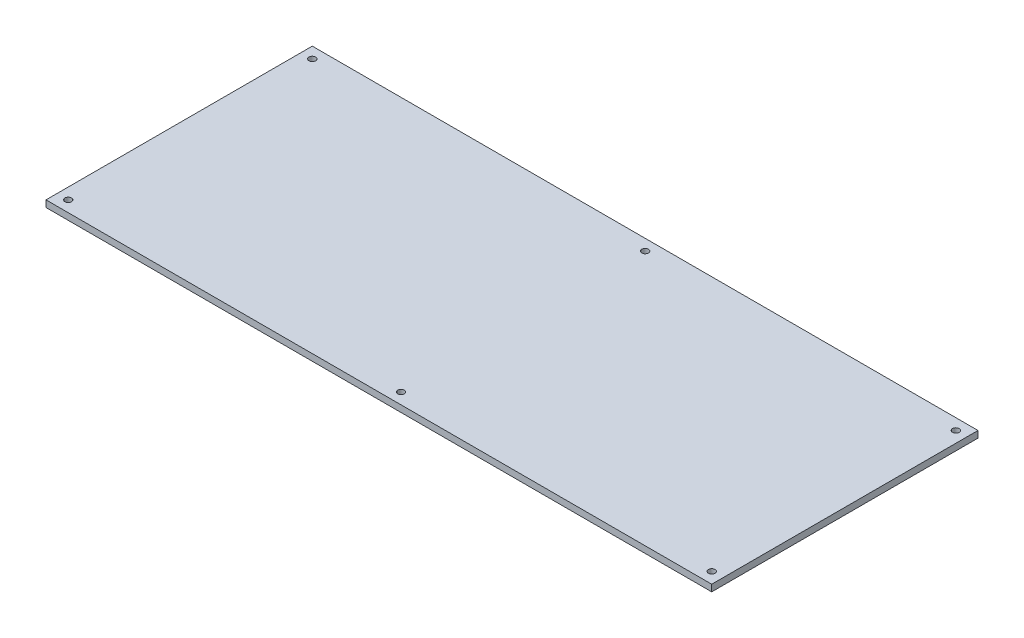
SolidWorks part; units mm, degrees
ref_plane "前视基准面" through (0, 0, 0) normal (0, 0, 1) x (1, 0, 0)
ref_plane "上视基准面" through (0, 0, 0) normal (0, 1, 0) x (1, 0, 0)
ref_plane "右视基准面" through (0, 0, 0) normal (1, 0, 0) x (0, 0, -1)
sketch "Sketch1" plane through (0, 0, 0) normal (0, 1, 0) x (1, 0, 0)
  line L0 (0, 0) -> (0, 75.008) construction
  line L1 (-150, 60) -> (150, 60)
  line L2 (-150, 60) -> (-150, -60)
  line L3 (-150, -60) -> (150, -60)
  line L4 (150, 60) -> (150, -60)
  line L5 (-150, 60) -> (150, -60) construction
  line L6 (-150, -60) -> (150, 60) construction
  line L7 (0, 0) -> (62.2631, 0) construction
  circle A0 centre (-145, 55) radius 1.5
  circle A2 centre (145, 55) radius 1.5
  circle A3 centre (-145, -55) radius 1.5
  circle A4 centre (145, -55) radius 1.5
  circle A5 centre (5, -55) radius 1.5
  circle A6 centre (5, 55) radius 1.5
  point P0 (0, 0)
  dimension "D3" = 3
  dimension "D7" = 140
  dimension "D1" = 300
  dimension "D2" = 120
  dimension "D4" = 5
  dimension "D5" = 5
  dimension "D6" = 2
extrude "Boss-Extrude1" add sketch "Sketch1" along normal blind 3
